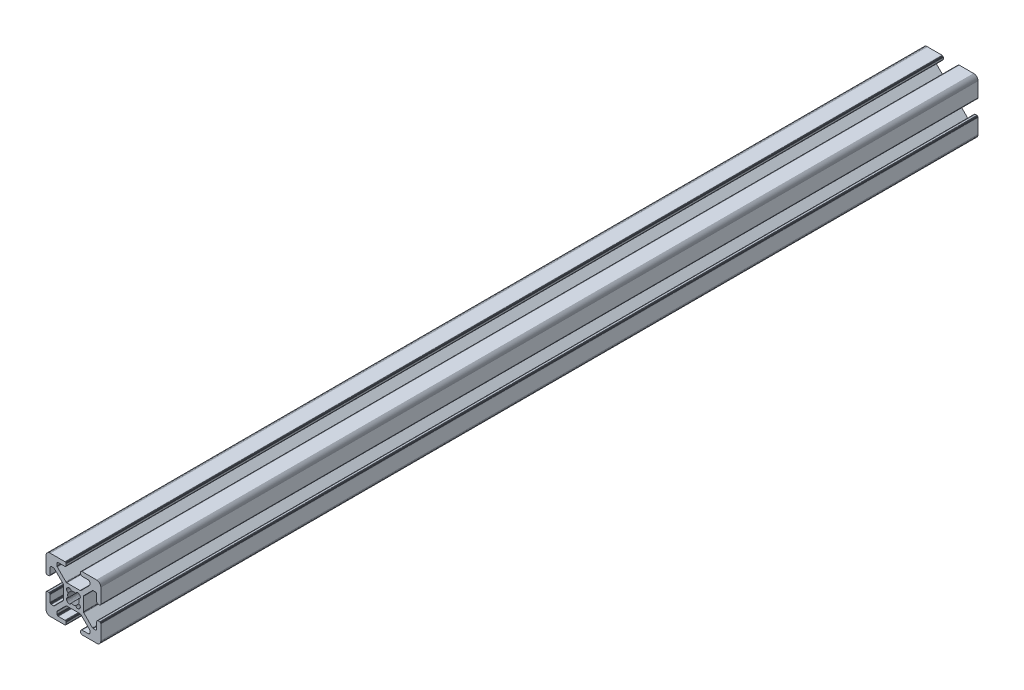
SolidWorks part; units mm, degrees
ref_plane "Front Plane" through (0, 0, 0) normal (0, 0, 1) x (1, 0, 0)
ref_plane "Top Plane" through (0, 0, 0) normal (0, 1, 0) x (1, 0, 0)
ref_plane "Right Plane" through (0, 0, 0) normal (1, 0, 0) x (0, 0, -1)
sketch "Model" plane through (0, 0, 0) normal (0, 0, 1) x (1, 0, 0)
  line L0 (949.3185, 626.4911) -> (949.2982, 626.4765)
  line L1 (949.2789, 626.4607) -> (949.2607, 626.4437)
  line L2 (946.8251, 623.8967) -> (946.8226, 623.8719)
  line L3 (949.2982, 626.4765) -> (949.2789, 626.4607)
  line L4 (946.9334, 624.1164) -> (949.2607, 626.4437)
  line L5 (949.3616, 626.516) -> (949.3396, 626.5042)
  line L6 (951.5709, 615.5372) -> (951.5806, 615.684)
  line L7 (946.2883, 614.588) -> (946.3355, 614.572)
  line L8 (946.8218, 620.2711) -> (946.8218, 623.847)
  line L9 (946.2436, 614.6101) -> (946.2883, 614.588)
  line L10 (948.4981, 615.8331) -> (948.5258, 615.8745)
  line L11 (946.1647, 614.6706) -> (946.2021, 614.6378)
  line L12 (946.842, 620.1486) -> (946.8508, 620.1253)
  line L13 (950.5066, 619.896) -> (950.4846, 619.8513)
  line L14 (946.2021, 614.6378) -> (946.2436, 614.6101)
  line L15 (950.5343, 619.9375) -> (950.5066, 619.896)
  line L16 (949.3396, 617.6138) -> (949.3616, 617.6021)
  line L17 (950.4685, 619.8041) -> (950.4588, 619.7553)
  line L18 (950.4588, 619.7553) -> (950.4556, 619.7055)
  line L19 (951.1996, 620.0865) -> (950.8366, 620.0865)
  line L20 (944.0806, 620.4874) -> (944.1836, 620.4908)
  line L21 (946.1379, 619.2062) -> (946.1197, 619.2232)
  line L22 (945.991, 619.2976) -> (945.9671, 619.3048)
  line L23 (950.2651, 617.6138) -> (950.3065, 617.6415)
  line L24 (950.2204, 617.5918) -> (950.2651, 617.6138)
  line L25 (945.0007, 623.9018) -> (944.9113, 623.8486)
  line L26 (951.3454, 620.0575) -> (951.2982, 620.0735)
  line L27 (950.5672, 624.1431) -> (950.6046, 624.1103)
  line L28 (950.5343, 624.1806) -> (950.5672, 624.1431)
  line L29 (946.0531, 614.94) -> (946.0563, 614.8903)
  line L30 (949.4804, 617.566) -> (949.5052, 617.5636)
  line L31 (945.0979, 623.9385) -> (945.0007, 623.9018)
  line L32 (946.1318, 628.5831) -> (946.1647, 628.5456)
  line L33 (946.1041, 628.6245) -> (946.1318, 628.5831)
  line L34 (950.344, 617.6744) -> (950.3768, 617.7118)
  line L35 (948.2455, 628.4308) -> (948.1958, 628.434)
  line L36 (948.2944, 628.421) -> (948.2455, 628.4308)
  line L37 (949.3185, 617.627) -> (949.3396, 617.6138)
  line L38 (950.6046, 620.0078) -> (950.5672, 619.9749)
  line L39 (951.5806, 628.434) -> (951.5709, 628.5809)
  line L40 (950.4266, 626.3201) -> (950.4045, 626.3648)
  line L41 (945.8701, 622.8898) -> (945.9233, 622.9791)
  line L42 (950.4426, 626.2729) -> (950.4266, 626.3201)
  line L43 (951.2511, 629.2295) -> (951.1404, 629.3265)
  line L44 (950.6046, 624.1103) -> (950.6461, 624.0826)
  line L45 (946.4341, 614.559) -> (950.4556, 614.559)
  line L46 (951.1404, 614.7915) -> (951.2511, 614.8885)
  line L47 (950.3065, 617.6415) -> (950.344, 617.6744)
  line L48 (950.6461, 624.0826) -> (950.6908, 624.0605)
  line L49 (948.4652, 628.3224) -> (948.4278, 628.3553)
  line L50 (945.8934, 619.317) -> (945.8685, 619.3178)
  line L51 (944.2863, 620.5009) -> (944.388, 620.5178)
  line L52 (951.5806, 619.7055) -> (951.5773, 619.7553)
  line L53 (950.738, 624.0445) -> (950.7868, 624.0348)
  line L54 (950.4588, 624.3628) -> (950.4685, 624.3139)
  line L55 (946.2021, 615.6053) -> (946.1647, 615.5724)
  line L56 (944.7673, 620.4183) -> (944.8328, 620.3375)
  line L57 (944.7171, 620.5093) -> (944.7673, 620.4183)
  line L58 (946.1647, 615.5724) -> (946.1318, 615.535)
  line L59 (950.8861, 629.4734) -> (950.7467, 629.5207)
  line L60 (944.6835, 620.6077) -> (944.7171, 620.5093)
  line L61 (950.4846, 624.2667) -> (950.5066, 624.222)
  line L62 (946.8226, 620.2462) -> (946.8251, 620.2214)
  line L63 (950.4685, 624.3139) -> (950.4846, 624.2667)
  line L64 (951.4315, 624.1103) -> (951.469, 624.1431)
  line L65 (946.1318, 615.535) -> (946.1041, 615.4935)
  line L66 (950.6024, 629.5494) -> (950.4556, 629.559)
  line L67 (951.5018, 624.1806) -> (951.5295, 624.222)
  line L68 (951.5806, 624.4125) -> (951.5806, 628.434)
  line L69 (950.5066, 624.222) -> (950.5343, 624.1806)
  line L70 (951.5295, 624.222) -> (951.5516, 624.2667)
  line L71 (944.0806, 619.3178) -> (945.8685, 619.3178)
  line L72 (951.5516, 624.2667) -> (951.5676, 624.3139)
  line L73 (951.469, 624.1431) -> (951.5018, 624.1806)
  line L74 (951.1404, 629.3265) -> (951.0181, 629.4083)
  line L75 (948.5258, 627.3181) -> (948.5375, 627.3401)
  line L76 (946.0821, 629.3238) -> (946.066, 629.2766)
  line L77 (951.5709, 628.5809) -> (951.5422, 628.7252)
  line L78 (945.9182, 619.3145) -> (945.8934, 619.317)
  line L79 (944.8328, 620.3375) -> (944.9113, 620.2695)
  line L80 (951.5422, 628.7252) -> (951.4949, 628.8645)
  line L81 (948.4652, 627.2392) -> (948.4823, 627.2574)
  line L82 (945.9428, 619.3105) -> (945.9182, 619.3145)
  line L83 (950.4556, 629.559) -> (946.4341, 629.559)
  line L84 (948.4981, 628.285) -> (948.4652, 628.3224)
  line L85 (946.1004, 624.879) -> (946.1197, 624.8948)
  line L86 (945.0007, 620.2163) -> (945.0979, 620.1796)
  line L87 (946.3843, 615.6808) -> (946.3355, 615.671)
  line L88 (948.1958, 615.684) -> (948.2455, 615.6873)
  line L89 (946.886, 620.0594) -> (946.9005, 620.0391)
  line L90 (946.9164, 624.0982) -> (946.9005, 624.0789)
  line L91 (949.3843, 626.5263) -> (949.3616, 626.516)
  line L92 (946.3355, 629.546) -> (946.2883, 629.53)
  line L93 (949.4558, 626.548) -> (949.4315, 626.5423)
  line L94 (950.6024, 614.5686) -> (950.7467, 614.5974)
  line L95 (946.4341, 629.559) -> (946.3843, 629.5558)
  line L96 (951.1996, 624.0315) -> (951.2493, 624.0348)
  line L97 (946.3843, 629.5558) -> (946.3355, 629.546)
  line L98 (946.1647, 628.5456) -> (946.2021, 628.5128)
  line L99 (950.0746, 617.5628) -> (949.5301, 617.5628)
  line L100 (950.0746, 617.5628) -> (950.1243, 617.566)
  line L101 (946.2021, 628.5128) -> (946.2436, 628.4851)
  line L102 (946.2883, 629.53) -> (946.2436, 629.508)
  line L103 (946.8611, 624.0155) -> (946.8508, 623.9928)
  line L104 (950.4523, 617.894) -> (950.4556, 617.9438)
  line L105 (946.8508, 623.9928) -> (946.842, 623.9694)
  line L106 (951.2493, 620.0833) -> (951.1996, 620.0865)
  line L107 (951.2982, 620.0735) -> (951.2493, 620.0833)
  line L108 (945.5945, 623.8542) -> (945.5044, 623.9059)
  line L109 (950.6461, 620.0355) -> (950.6046, 620.0078)
  line L110 (946.1318, 629.41) -> (946.1041, 629.3685)
  line L111 (945.6742, 623.7874) -> (945.5945, 623.8542)
  line L112 (946.1041, 629.3685) -> (946.0821, 629.3238)
  line L113 (951.5773, 619.7553) -> (951.5676, 619.8041)
  line L114 (948.5478, 628.1988) -> (948.5258, 628.2435)
  line L115 (948.5638, 628.1516) -> (948.5478, 628.1988)
  line L116 (950.4556, 626.1743) -> (950.4556, 624.4125)
  line L117 (945.9233, 622.9791) -> (945.96, 623.0764)
  line L118 (944.9113, 620.2695) -> (945.0007, 620.2163)
  line L119 (948.5566, 627.3861) -> (948.5638, 627.41)
  line L120 (946.3843, 614.5623) -> (946.4341, 614.559)
  line L121 (948.5736, 628.1028) -> (948.5638, 628.1516)
  line L122 (945.9233, 621.1389) -> (945.8701, 621.2282)
  line L123 (950.344, 626.4437) -> (950.3065, 626.4765)
  line L124 (945.991, 624.8205) -> (946.0143, 624.8293)
  line L125 (951.5676, 624.3139) -> (951.5773, 624.3628)
  line L126 (948.5478, 616.7553) -> (948.5375, 616.778)
  line L127 (948.5768, 616.6095) -> (948.5768, 616.065)
  line L128 (945.9671, 624.8133) -> (945.991, 624.8205)
  line L129 (946.3355, 614.572) -> (946.3843, 614.5623)
  line L130 (945.6387, 622.2647) -> (945.6218, 622.3665)
  line L131 (948.4652, 615.7956) -> (948.4981, 615.8331)
  line L132 (948.5566, 616.7319) -> (948.5478, 616.7553)
  line L133 (948.576, 627.4837) -> (948.5768, 627.5086)
  line L134 (945.9671, 619.3048) -> (945.9428, 619.3105)
  line L135 (946.059, 624.8513) -> (946.0802, 624.8645)
  line L136 (946.3355, 628.447) -> (946.3843, 628.4373)
  line L137 (951.3481, 629.1189) -> (951.2511, 629.2295)
  line L138 (948.5768, 628.053) -> (948.5768, 627.5086)
  line L139 (944.5871, 623.5468) -> (944.4884, 623.5768)
  line L140 (945.6303, 622.6955) -> (945.7213, 622.7458)
  line L141 (950.4045, 617.7533) -> (950.4266, 617.798)
  line L142 (945.9791, 623.1786) -> (945.9799, 623.2825)
  line L143 (945.9799, 623.2825) -> (945.9625, 623.385)
  line L144 (945.8021, 622.8112) -> (945.8701, 622.8898)
  line L145 (945.96, 623.0764) -> (945.9791, 623.1786)
  line L146 (945.7213, 622.7458) -> (945.8021, 622.8112)
  line L147 (950.1243, 617.566) -> (950.1732, 617.5758)
  line L148 (948.5638, 616.7081) -> (948.5566, 616.7319)
  line L149 (946.2436, 628.4851) -> (946.2883, 628.463)
  line L150 (948.5695, 627.4343) -> (948.5736, 627.4589)
  line L151 (946.1647, 629.4474) -> (946.1318, 629.41)
  line L152 (945.6742, 620.3306) -> (945.8089, 620.4653)
  line L153 (945.8757, 623.573) -> (945.8089, 623.6527)
  line L154 (946.2436, 629.508) -> (946.2021, 629.4803)
  line L155 (945.6218, 621.7516) -> (945.6387, 621.8533)
  line L156 (948.5126, 627.2969) -> (948.5258, 627.3181)
  line L157 (948.5638, 627.41) -> (948.5695, 627.4343)
  line L158 (948.5736, 627.4589) -> (948.576, 627.4837)
  line L159 (945.5044, 620.2122) -> (945.5945, 620.2639)
  line L160 (950.4426, 617.8452) -> (950.4523, 617.894)
  line L161 (946.1197, 624.8948) -> (946.1379, 624.9119)
  line L162 (945.5945, 620.2639) -> (945.6742, 620.3306)
  line L163 (950.3065, 626.4765) -> (950.2651, 626.5042)
  line L164 (946.4341, 615.684) -> (946.3843, 615.6808)
  line L165 (944.7673, 623.6998) -> (944.7171, 623.6088)
  line L166 (945.8757, 620.545) -> (945.9274, 620.6352)
  line L167 (948.5478, 615.9192) -> (948.5638, 615.9664)
  line L168 (945.9274, 620.6352) -> (945.9625, 620.7331)
  line L169 (950.1732, 626.5423) -> (950.1243, 626.552)
  line L170 (948.576, 616.6344) -> (948.5736, 616.6592)
  line L171 (950.1243, 626.552) -> (950.0746, 626.5553)
  line L172 (948.4981, 627.2766) -> (948.5126, 627.2969)
  line L173 (948.5258, 628.2435) -> (948.4981, 628.285)
  line L174 (948.5768, 628.053) -> (948.5736, 628.1028)
  line L175 (951.5516, 619.8513) -> (951.5295, 619.896)
  line L176 (951.5676, 619.8041) -> (951.5516, 619.8513)
  line L177 (946.0563, 615.3528) -> (946.0531, 615.303)
  line L178 (946.1041, 615.4935) -> (946.0821, 615.4488)
  line L179 (945.6387, 621.8533) -> (945.6488, 621.956)
  line L180 (946.037, 624.8396) -> (946.059, 624.8513)
  line L181 (950.4523, 626.224) -> (950.4426, 626.2729)
  line L182 (951.5773, 624.3628) -> (951.5806, 624.4125)
  line L183 (946.0531, 615.303) -> (946.0531, 614.94)
  line L184 (946.9005, 624.0789) -> (946.886, 624.0586)
  line L185 (946.0821, 615.4488) -> (946.066, 615.4016)
  line L186 (951.0181, 629.4083) -> (950.8861, 629.4734)
  line L187 (948.1958, 615.684) -> (946.4341, 615.684)
  line L188 (951.2982, 624.0445) -> (951.3454, 624.0605)
  line L189 (944.1836, 620.4908) -> (944.2863, 620.5009)
  line L190 (950.7467, 629.5207) -> (950.6024, 629.5494)
  line L191 (948.5375, 627.3401) -> (948.5478, 627.3628)
  line L192 (950.5672, 619.9749) -> (950.5343, 619.9375)
  line L193 (950.7868, 624.0348) -> (950.8366, 624.0315)
  line L194 (946.0531, 629.178) -> (946.0531, 628.815)
  line L195 (951.4949, 628.8645) -> (951.4298, 628.9965)
  line L196 (945.4065, 623.941) -> (945.3041, 623.9584)
  line L197 (945.8701, 621.2282) -> (945.8021, 621.3068)
  line L198 (950.3768, 626.4062) -> (950.344, 626.4437)
  line L199 (945.3041, 623.9584) -> (945.2001, 623.9575)
  line L200 (945.9625, 620.7331) -> (945.9799, 620.8355)
  line L201 (945.8089, 620.4653) -> (945.8757, 620.545)
  line L202 (948.2944, 615.697) -> (948.3416, 615.713)
  line L203 (948.2455, 615.6873) -> (948.2944, 615.697)
  line L204 (949.4804, 626.552) -> (949.4558, 626.548)
  line L205 (950.2204, 626.5263) -> (950.1732, 626.5423)
  line L206 (948.3416, 615.713) -> (948.3863, 615.7351)
  line L207 (945.7213, 621.3723) -> (945.6303, 621.4225)
  line L208 (950.4556, 626.1743) -> (950.4523, 626.224)
  line L209 (945.9799, 620.8355) -> (945.9791, 620.9395)
  line L210 (948.5768, 616.6095) -> (948.576, 616.6344)
  line L211 (948.5258, 615.8745) -> (948.5478, 615.9192)
  line L212 (945.9428, 624.8076) -> (945.9671, 624.8133)
  line L213 (945.2001, 623.9575) -> (945.0979, 623.9385)
  line L214 (945.96, 621.0417) -> (945.9233, 621.1389)
  line L215 (951.3454, 624.0605) -> (951.3901, 624.0826)
  line L216 (946.0802, 624.8645) -> (946.1004, 624.879)
  line L217 (951.5422, 615.3929) -> (951.5709, 615.5372)
  line L218 (945.6218, 622.3665) -> (945.5983, 622.4669)
  line L219 (951.3901, 624.0826) -> (951.4315, 624.1103)
  line L220 (949.5052, 626.5545) -> (949.4804, 626.552)
  line L221 (945.9791, 620.9395) -> (945.96, 621.0417)
  line L222 (946.0143, 619.2888) -> (945.991, 619.2976)
  line L223 (951.2493, 624.0348) -> (951.2982, 624.0445)
  line L224 (946.1197, 619.2232) -> (946.1004, 619.239)
  line L225 (951.4298, 628.9965) -> (951.3481, 629.1189)
  line L226 (951.2511, 614.8885) -> (951.3481, 614.9992)
  line L227 (946.1318, 614.7081) -> (946.1647, 614.6706)
  line L228 (944.6835, 623.5104) -> (944.5871, 623.5468)
  line L229 (948.5478, 627.3628) -> (948.5566, 627.3861)
  line L230 (950.4556, 624.4125) -> (950.4588, 624.3628)
  line L231 (946.0563, 629.2278) -> (946.0531, 629.178)
  line L232 (946.066, 629.2766) -> (946.0563, 629.2278)
  line L233 (944.388, 620.5178) -> (944.4884, 620.5412)
  line L234 (945.8685, 624.8003) -> (944.0806, 624.8003)
  line L235 (946.1004, 619.239) -> (946.0802, 619.2536)
  line L236 (951.4298, 615.1215) -> (951.4949, 615.2535)
  line L237 (946.3843, 628.4373) -> (946.4341, 628.434)
  line L238 (944.4884, 620.5412) -> (944.5871, 620.5713)
  line L239 (944.5871, 620.5713) -> (944.6835, 620.6077)
  line L240 (946.8291, 620.1968) -> (946.8348, 620.1725)
  line L241 (946.8508, 620.1253) -> (946.8611, 620.1026)
  line L242 (946.8218, 620.2711) -> (946.8226, 620.2462)
  line L243 (946.8226, 623.8719) -> (946.8218, 623.847)
  line L244 (946.8291, 623.9213) -> (946.8251, 623.8967)
  line L245 (949.4315, 626.5423) -> (949.4077, 626.5351)
  line L246 (949.4077, 626.5351) -> (949.3843, 626.5263)
  line L247 (949.3396, 626.5042) -> (949.3185, 626.4911)
  line L248 (946.9334, 624.1164) -> (946.9164, 624.0982)
  line L249 (944.1836, 623.6273) -> (944.0806, 623.6307)
  line L250 (951.5295, 619.896) -> (951.5018, 619.9375)
  line L251 (944.388, 623.6003) -> (944.2863, 623.6171)
  line L252 (950.4266, 617.798) -> (950.4426, 617.8452)
  line L253 (946.842, 623.9694) -> (946.8348, 623.9456)
  line L254 (950.4556, 619.7055) -> (950.4556, 617.9438)
  line L255 (949.2789, 617.6573) -> (949.2982, 617.6415)
  line L256 (946.8611, 620.1026) -> (946.8729, 620.0806)
  line L257 (946.8348, 620.1725) -> (946.842, 620.1486)
  line L258 (949.2607, 617.6744) -> (946.9334, 620.0017)
  line L259 (945.6522, 622.059) -> (945.6488, 622.1621)
  line L260 (945.6488, 621.956) -> (945.6522, 622.059)
  line L261 (946.1041, 614.7495) -> (946.1318, 614.7081)
  line L262 (944.8328, 623.7805) -> (944.7673, 623.6998)
  line L263 (946.0821, 614.7942) -> (946.1041, 614.7495)
  line L264 (946.9164, 620.0199) -> (946.9334, 620.0017)
  line L265 (944.7171, 623.6088) -> (944.6835, 623.5104)
  line L266 (946.8729, 620.0806) -> (946.886, 620.0594)
  line L267 (945.5683, 622.5655) -> (945.5319, 622.662)
  line L268 (945.3041, 620.1597) -> (945.4065, 620.1771)
  line L269 (950.4556, 614.559) -> (950.6024, 614.5686)
  line L270 (945.6303, 621.4225) -> (945.5319, 621.456)
  line L271 (946.8251, 620.2214) -> (946.8291, 620.1968)
  line L272 (945.5983, 621.6512) -> (945.6218, 621.7516)
  line L273 (945.6488, 622.1621) -> (945.6387, 622.2647)
  line L274 (945.2001, 620.1605) -> (945.3041, 620.1597)
  line L275 (946.066, 614.8414) -> (946.0821, 614.7942)
  line L276 (951.5806, 615.684) -> (951.5806, 619.7055)
  line L277 (945.8685, 624.8003) -> (945.8934, 624.8011)
  line L278 (945.8934, 624.8011) -> (945.9182, 624.8035)
  line L279 (946.886, 624.0586) -> (946.8729, 624.0375)
  line L280 (946.8729, 624.0375) -> (946.8611, 624.0155)
  line L281 (948.5638, 615.9664) -> (948.5736, 616.0153)
  line L282 (948.4823, 627.2574) -> (948.4981, 627.2766)
  line L283 (950.8366, 624.0315) -> (951.1996, 624.0315)
  line L284 (945.5044, 623.9059) -> (945.4065, 623.941)
  line L285 (950.4846, 619.8513) -> (950.4685, 619.8041)
  line L286 (948.5736, 616.0153) -> (948.5768, 616.065)
  line L287 (945.8021, 621.3068) -> (945.7213, 621.3723)
  line L288 (950.8366, 620.0865) -> (950.7868, 620.0833)
  line L289 (946.8348, 623.9456) -> (946.8291, 623.9213)
  line L290 (949.5301, 626.5553) -> (950.0746, 626.5553)
  line L291 (945.5683, 621.5525) -> (945.5983, 621.6512)
  line L292 (949.2982, 617.6415) -> (949.3185, 617.627)
  line L293 (950.1732, 617.5758) -> (950.2204, 617.5918)
  line L294 (951.3901, 620.0355) -> (951.3454, 620.0575)
  line L295 (948.5375, 616.778) -> (948.5258, 616.8)
  line L296 (951.3481, 614.9992) -> (951.4298, 615.1215)
  line L297 (951.4315, 620.0078) -> (951.3901, 620.0355)
  line L298 (948.4981, 616.8414) -> (948.4823, 616.8607)
  line L299 (948.3416, 628.405) -> (948.2944, 628.421)
  line L300 (950.2651, 626.5042) -> (950.2204, 626.5263)
  line L301 (949.2607, 617.6744) -> (949.2789, 617.6573)
  line L302 (948.5126, 616.8211) -> (948.4981, 616.8414)
  line L303 (946.0531, 628.815) -> (946.0563, 628.7653)
  line L304 (951.469, 619.9749) -> (951.4315, 620.0078)
  line L305 (948.4652, 627.2392) -> (946.1379, 624.9119)
  line L306 (946.066, 615.4016) -> (946.0563, 615.3528)
  line L307 (950.7868, 620.0833) -> (950.738, 620.0735)
  line L308 (948.4823, 616.8607) -> (948.4652, 616.8789)
  line L309 (946.0563, 628.7653) -> (946.066, 628.7164)
  line L310 (951.5018, 619.9375) -> (951.469, 619.9749)
  line L311 (946.1379, 619.2062) -> (948.4652, 616.8789)
  line L312 (946.2883, 628.463) -> (946.3355, 628.447)
  line L313 (946.4341, 628.434) -> (948.1958, 628.434)
  line L314 (944.2863, 623.6171) -> (944.1836, 623.6273)
  line L315 (948.3863, 628.383) -> (948.3416, 628.405)
  line L316 (950.6908, 620.0575) -> (950.6461, 620.0355)
  line L317 (946.0143, 624.8293) -> (946.037, 624.8396)
  line L318 (950.738, 620.0735) -> (950.6908, 620.0575)
  line L319 (946.9005, 620.0391) -> (946.9164, 620.0199)
  line L320 (944.4884, 623.5768) -> (944.388, 623.6003)
  line L321 (950.3768, 617.7118) -> (950.4045, 617.7533)
  line L322 (948.4278, 628.3553) -> (948.3863, 628.383)
  line L323 (949.4558, 617.5701) -> (949.4804, 617.566)
  line L324 (949.5052, 617.5636) -> (949.5301, 617.5628)
  line L325 (946.066, 628.7164) -> (946.0821, 628.6692)
  line L326 (946.0821, 628.6692) -> (946.1041, 628.6245)
  line L327 (950.8861, 614.6447) -> (951.0181, 614.7097)
  line L328 (945.0979, 620.1796) -> (945.2001, 620.1605)
  line L329 (948.4278, 615.7628) -> (948.4652, 615.7956)
  line L330 (948.3863, 615.7351) -> (948.4278, 615.7628)
  line L331 (948.5736, 616.6592) -> (948.5695, 616.6838)
  line L332 (950.7467, 614.5974) -> (950.8861, 614.6447)
  line L333 (948.5695, 616.6838) -> (948.5638, 616.7081)
  line L334 (945.8089, 623.6527) -> (945.6742, 623.7874)
  line L335 (945.5319, 621.456) -> (945.5683, 621.5525)
  line L336 (945.9274, 623.4828) -> (945.8757, 623.573)
  line L337 (945.5983, 622.4669) -> (945.5683, 622.5655)
  line L338 (949.4077, 617.583) -> (949.4315, 617.5758)
  line L339 (949.4315, 617.5758) -> (949.4558, 617.5701)
  line L340 (945.9625, 623.385) -> (945.9274, 623.4828)
  line L341 (946.037, 619.2785) -> (946.0143, 619.2888)
  line L342 (946.0802, 619.2536) -> (946.059, 619.2667)
  line L343 (946.2436, 615.633) -> (946.2021, 615.6053)
  line L344 (944.9113, 623.8486) -> (944.8328, 623.7805)
  line L345 (950.6908, 624.0605) -> (950.738, 624.0445)
  line L346 (950.4045, 626.3648) -> (950.3768, 626.4062)
  line L347 (946.2021, 629.4803) -> (946.1647, 629.4474)
  line L348 (946.059, 619.2667) -> (946.037, 619.2785)
  line L349 (949.3843, 617.5918) -> (949.4077, 617.583)
  line L350 (946.0563, 614.8903) -> (946.066, 614.8414)
  line L351 (949.3616, 617.6021) -> (949.3843, 617.5918)
  line L352 (948.5258, 616.8) -> (948.5126, 616.8211)
  line L353 (945.4065, 620.1771) -> (945.5044, 620.2122)
  line L354 (949.5301, 626.5553) -> (949.5052, 626.5545)
  line L355 (951.4949, 615.2535) -> (951.5422, 615.3929)
  line L356 (945.5319, 622.662) -> (945.6303, 622.6955)
  line L357 (946.3355, 615.671) -> (946.2883, 615.655)
  line L358 (946.2883, 615.655) -> (946.2436, 615.633)
  line L359 (945.9182, 624.8035) -> (945.9428, 624.8076)
  line L360 (951.0181, 614.7097) -> (951.1404, 614.7915)
  line L361 (938.8427, 626.4911) -> (938.8629, 626.4765)
  line L362 (938.8822, 626.4607) -> (938.9004, 626.4437)
  line L363 (941.3361, 623.8967) -> (941.3385, 623.8719)
  line L364 (938.8629, 626.4765) -> (938.8822, 626.4607)
  line L365 (941.2277, 624.1164) -> (938.9004, 626.4437)
  line L366 (938.7995, 626.516) -> (938.8215, 626.5042)
  line L367 (936.5902, 615.5372) -> (936.5806, 615.684)
  line L368 (941.8729, 614.588) -> (941.8257, 614.572)
  line L369 (941.3393, 620.2711) -> (941.3393, 623.847)
  line L370 (941.9176, 614.6101) -> (941.8729, 614.588)
  line L371 (939.663, 615.8331) -> (939.6354, 615.8745)
  line L372 (941.9965, 614.6706) -> (941.959, 614.6378)
  line L373 (941.3191, 620.1486) -> (941.3103, 620.1253)
  line L374 (937.6545, 619.896) -> (937.6766, 619.8513)
  line L375 (941.959, 614.6378) -> (941.9176, 614.6101)
  line L376 (937.6268, 619.9375) -> (937.6545, 619.896)
  line L377 (938.8215, 617.6138) -> (938.7995, 617.6021)
  line L378 (937.6926, 619.8041) -> (937.7023, 619.7553)
  line L379 (937.7023, 619.7553) -> (937.7056, 619.7055)
  line L380 (936.9616, 620.0865) -> (937.3246, 620.0865)
  line L381 (944.0806, 620.4874) -> (943.9775, 620.4908)
  line L382 (942.0232, 619.2062) -> (942.0414, 619.2232)
  line L383 (942.1702, 619.2976) -> (942.194, 619.3048)
  line L384 (937.8961, 617.6138) -> (937.8546, 617.6415)
  line L385 (937.9408, 617.5918) -> (937.8961, 617.6138)
  line L386 (943.1605, 623.9018) -> (943.2498, 623.8486)
  line L387 (936.8158, 620.0575) -> (936.863, 620.0735)
  line L388 (937.594, 624.1431) -> (937.5565, 624.1103)
  line L389 (937.6268, 624.1806) -> (937.594, 624.1431)
  line L390 (942.1081, 614.94) -> (942.1048, 614.8903)
  line L391 (938.6807, 617.566) -> (938.6559, 617.5636)
  line L392 (943.0632, 623.9385) -> (943.1605, 623.9018)
  line L393 (942.0293, 628.5831) -> (941.9965, 628.5456)
  line L394 (942.057, 628.6245) -> (942.0293, 628.5831)
  line L395 (937.8172, 617.6744) -> (937.7843, 617.7118)
  line L396 (939.9156, 628.4308) -> (939.9653, 628.434)
  line L397 (939.8667, 628.421) -> (939.9156, 628.4308)
  line L398 (938.8427, 617.627) -> (938.8215, 617.6138)
  line L399 (937.5565, 620.0078) -> (937.594, 619.9749)
  line L400 (936.5806, 628.434) -> (936.5902, 628.5809)
  line L401 (937.7346, 626.3201) -> (937.7566, 626.3648)
  line L402 (942.291, 622.8898) -> (942.2378, 622.9791)
  line L403 (937.7185, 626.2729) -> (937.7346, 626.3201)
  line L404 (936.9101, 629.2295) -> (937.0207, 629.3265)
  line L405 (937.5565, 624.1103) -> (937.5151, 624.0826)
  line L406 (941.7271, 614.559) -> (937.7056, 614.559)
  line L407 (937.0207, 614.7915) -> (936.9101, 614.8885)
  line L408 (937.8546, 617.6415) -> (937.8172, 617.6744)
  line L409 (937.5151, 624.0826) -> (937.4704, 624.0605)
  line L410 (939.6959, 628.3224) -> (939.7334, 628.3553)
  line L411 (942.2677, 619.317) -> (942.2926, 619.3178)
  line L412 (943.8749, 620.5009) -> (943.7731, 620.5178)
  line L413 (936.5806, 619.7055) -> (936.5838, 619.7553)
  line L414 (937.4232, 624.0445) -> (937.3743, 624.0348)
  line L415 (937.7023, 624.3628) -> (937.6926, 624.3139)
  line L416 (941.959, 615.6053) -> (941.9965, 615.5724)
  line L417 (943.3938, 620.4183) -> (943.3284, 620.3375)
  line L418 (943.4441, 620.5093) -> (943.3938, 620.4183)
  line L419 (941.9965, 615.5724) -> (942.0293, 615.535)
  line L420 (937.275, 629.4734) -> (937.4144, 629.5207)
  line L421 (943.4776, 620.6077) -> (943.4441, 620.5093)
  line L422 (937.6766, 624.2667) -> (937.6545, 624.222)
  line L423 (941.3385, 620.2462) -> (941.3361, 620.2214)
  line L424 (937.6926, 624.3139) -> (937.6766, 624.2667)
  line L425 (936.7296, 624.1103) -> (936.6922, 624.1431)
  line L426 (942.0293, 615.535) -> (942.057, 615.4935)
  line L427 (937.5587, 629.5494) -> (937.7056, 629.559)
  line L428 (936.6593, 624.1806) -> (936.6316, 624.222)
  line L429 (936.5806, 624.4125) -> (936.5806, 628.434)
  line L430 (937.6545, 624.222) -> (937.6268, 624.1806)
  line L431 (936.6316, 624.222) -> (936.6096, 624.2667)
  line L432 (944.0806, 619.3178) -> (942.2926, 619.3178)
  line L433 (936.6096, 624.2667) -> (936.5935, 624.3139)
  line L434 (936.6922, 624.1431) -> (936.6593, 624.1806)
  line L435 (937.0207, 629.3265) -> (937.1431, 629.4083)
  line L436 (939.6354, 627.3181) -> (939.6236, 627.3401)
  line L437 (942.0791, 629.3238) -> (942.0951, 629.2766)
  line L438 (936.5902, 628.5809) -> (936.6189, 628.7252)
  line L439 (942.2429, 619.3145) -> (942.2677, 619.317)
  line L440 (943.3284, 620.3375) -> (943.2498, 620.2695)
  line L441 (936.6189, 628.7252) -> (936.6662, 628.8645)
  line L442 (939.6959, 627.2392) -> (939.6789, 627.2574)
  line L443 (942.2183, 619.3105) -> (942.2429, 619.3145)
  line L444 (937.7056, 629.559) -> (941.7271, 629.559)
  line L445 (939.663, 628.285) -> (939.6959, 628.3224)
  line L446 (942.0607, 624.879) -> (942.0414, 624.8948)
  line L447 (943.1605, 620.2163) -> (943.0632, 620.1796)
  line L448 (941.7768, 615.6808) -> (941.8257, 615.671)
  line L449 (939.9653, 615.684) -> (939.9156, 615.6873)
  line L450 (941.2751, 620.0594) -> (941.2606, 620.0391)
  line L451 (941.2448, 624.0982) -> (941.2606, 624.0789)
  line L452 (938.7768, 626.5263) -> (938.7995, 626.516)
  line L453 (941.8257, 629.546) -> (941.8729, 629.53)
  line L454 (938.7053, 626.548) -> (938.7296, 626.5423)
  line L455 (937.5587, 614.5686) -> (937.4144, 614.5974)
  line L456 (941.7271, 629.559) -> (941.7768, 629.5558)
  line L457 (936.9616, 624.0315) -> (936.9118, 624.0348)
  line L458 (941.7768, 629.5558) -> (941.8257, 629.546)
  line L459 (941.9965, 628.5456) -> (941.959, 628.5128)
  line L460 (938.0866, 617.5628) -> (938.631, 617.5628)
  line L461 (938.0866, 617.5628) -> (938.0368, 617.566)
  line L462 (941.959, 628.5128) -> (941.9176, 628.4851)
  line L463 (941.8729, 629.53) -> (941.9176, 629.508)
  line L464 (941.3, 624.0155) -> (941.3103, 623.9928)
  line L465 (937.7088, 617.894) -> (937.7056, 617.9438)
  line L466 (941.3103, 623.9928) -> (941.3191, 623.9694)
  line L467 (936.9118, 620.0833) -> (936.9616, 620.0865)
  line L468 (936.863, 620.0735) -> (936.9118, 620.0833)
  line L469 (942.5666, 623.8542) -> (942.6567, 623.9059)
  line L470 (937.5151, 620.0355) -> (937.5565, 620.0078)
  line L471 (942.0293, 629.41) -> (942.057, 629.3685)
  line L472 (942.4869, 623.7874) -> (942.5666, 623.8542)
  line L473 (942.057, 629.3685) -> (942.0791, 629.3238)
  line L474 (936.5838, 619.7553) -> (936.5935, 619.8041)
  line L475 (939.6133, 628.1988) -> (939.6354, 628.2435)
  line L476 (939.5973, 628.1516) -> (939.6133, 628.1988)
  line L477 (937.7056, 626.1743) -> (937.7056, 624.4125)
  line L478 (942.2378, 622.9791) -> (942.2011, 623.0764)
  line L479 (943.2498, 620.2695) -> (943.1605, 620.2163)
  line L480 (939.6045, 627.3861) -> (939.5973, 627.41)
  line L481 (941.7768, 614.5623) -> (941.7271, 614.559)
  line L482 (939.5876, 628.1028) -> (939.5973, 628.1516)
  line L483 (942.2378, 621.1389) -> (942.291, 621.2282)
  line L484 (937.8172, 626.4437) -> (937.8546, 626.4765)
  line L485 (942.1702, 624.8205) -> (942.1468, 624.8293)
  line L486 (936.5935, 624.3139) -> (936.5838, 624.3628)
  line L487 (939.6133, 616.7553) -> (939.6236, 616.778)
  line L488 (939.5843, 616.6095) -> (939.5843, 616.065)
  line L489 (942.194, 624.8133) -> (942.1702, 624.8205)
  line L490 (941.8257, 614.572) -> (941.7768, 614.5623)
  line L491 (942.5225, 622.2647) -> (942.5393, 622.3665)
  line L492 (939.6959, 615.7956) -> (939.663, 615.8331)
  line L493 (939.6045, 616.7319) -> (939.6133, 616.7553)
  line L494 (939.5851, 627.4837) -> (939.5843, 627.5086)
  line L495 (942.194, 619.3048) -> (942.2183, 619.3105)
  line L496 (942.1021, 624.8513) -> (942.081, 624.8645)
  line L497 (941.8257, 628.447) -> (941.7768, 628.4373)
  line L498 (936.813, 629.1189) -> (936.9101, 629.2295)
  line L499 (939.5843, 628.053) -> (939.5843, 627.5086)
  line L500 (943.5741, 623.5468) -> (943.6727, 623.5768)
  line L501 (942.5308, 622.6955) -> (942.4398, 622.7458)
  line L502 (937.7566, 617.7533) -> (937.7346, 617.798)
  line L503 (942.182, 623.1786) -> (942.1812, 623.2825)
  line L504 (942.1812, 623.2825) -> (942.1986, 623.385)
  line L505 (942.359, 622.8112) -> (942.291, 622.8898)
  line L506 (942.2011, 623.0764) -> (942.182, 623.1786)
  line L507 (942.4398, 622.7458) -> (942.359, 622.8112)
  line L508 (938.0368, 617.566) -> (937.988, 617.5758)
  line L509 (939.5973, 616.7081) -> (939.6045, 616.7319)
  line L510 (941.9176, 628.4851) -> (941.8729, 628.463)
  line L511 (939.5916, 627.4343) -> (939.5876, 627.4589)
  line L512 (941.9965, 629.4474) -> (942.0293, 629.41)
  line L513 (942.4869, 620.3306) -> (942.3522, 620.4653)
  line L514 (942.2854, 623.573) -> (942.3522, 623.6527)
  line L515 (941.9176, 629.508) -> (941.959, 629.4803)
  line L516 (942.5393, 621.7516) -> (942.5225, 621.8533)
  line L517 (939.6485, 627.2969) -> (939.6354, 627.3181)
  line L518 (939.5973, 627.41) -> (939.5916, 627.4343)
  line L519 (939.5876, 627.4589) -> (939.5851, 627.4837)
  line L520 (942.6567, 620.2122) -> (942.5666, 620.2639)
  line L521 (937.7185, 617.8452) -> (937.7088, 617.894)
  line L522 (942.0414, 624.8948) -> (942.0232, 624.9119)
  line L523 (942.5666, 620.2639) -> (942.4869, 620.3306)
  line L524 (937.8546, 626.4765) -> (937.8961, 626.5042)
  line L525 (941.7271, 615.684) -> (941.7768, 615.6808)
  line L526 (943.3938, 623.6998) -> (943.4441, 623.6088)
  line L527 (942.2854, 620.545) -> (942.2337, 620.6352)
  line L528 (939.6133, 615.9192) -> (939.5973, 615.9664)
  line L529 (942.2337, 620.6352) -> (942.1986, 620.7331)
  line L530 (937.988, 626.5423) -> (938.0368, 626.552)
  line L531 (939.5851, 616.6344) -> (939.5876, 616.6592)
  line L532 (938.0368, 626.552) -> (938.0866, 626.5553)
  line L533 (939.663, 627.2766) -> (939.6485, 627.2969)
  line L534 (939.6354, 628.2435) -> (939.663, 628.285)
  line L535 (939.5843, 628.053) -> (939.5876, 628.1028)
  line L536 (936.6096, 619.8513) -> (936.6316, 619.896)
  line L537 (936.5935, 619.8041) -> (936.6096, 619.8513)
  line L538 (942.1048, 615.3528) -> (942.1081, 615.303)
  line L539 (942.057, 615.4935) -> (942.0791, 615.4488)
  line L540 (942.5225, 621.8533) -> (942.5123, 621.956)
  line L541 (942.1241, 624.8396) -> (942.1021, 624.8513)
  line L542 (937.7088, 626.224) -> (937.7185, 626.2729)
  line L543 (936.5838, 624.3628) -> (936.5806, 624.4125)
  line L544 (942.1081, 615.303) -> (942.1081, 614.94)
  line L545 (941.2606, 624.0789) -> (941.2751, 624.0586)
  line L546 (942.0791, 615.4488) -> (942.0951, 615.4016)
  line L547 (937.1431, 629.4083) -> (937.275, 629.4734)
  line L548 (939.9653, 615.684) -> (941.7271, 615.684)
  line L549 (936.863, 624.0445) -> (936.8158, 624.0605)
  line L550 (943.9775, 620.4908) -> (943.8749, 620.5009)
  line L551 (937.4144, 629.5207) -> (937.5587, 629.5494)
  line L552 (939.6236, 627.3401) -> (939.6133, 627.3628)
  line L553 (937.594, 619.9749) -> (937.6268, 619.9375)
  line L554 (937.3743, 624.0348) -> (937.3246, 624.0315)
  line L555 (942.1081, 629.178) -> (942.1081, 628.815)
  line L556 (936.6662, 628.8645) -> (936.7313, 628.9965)
  line L557 (942.7546, 623.941) -> (942.8571, 623.9584)
  line L558 (942.291, 621.2282) -> (942.359, 621.3068)
  line L559 (937.7843, 626.4062) -> (937.8172, 626.4437)
  line L560 (942.8571, 623.9584) -> (942.961, 623.9575)
  line L561 (942.1986, 620.7331) -> (942.1812, 620.8355)
  line L562 (942.3522, 620.4653) -> (942.2854, 620.545)
  line L563 (939.8667, 615.697) -> (939.8195, 615.713)
  line L564 (939.9156, 615.6873) -> (939.8667, 615.697)
  line L565 (938.6807, 626.552) -> (938.7053, 626.548)
  line L566 (937.9408, 626.5263) -> (937.988, 626.5423)
  line L567 (939.8195, 615.713) -> (939.7748, 615.7351)
  line L568 (942.4398, 621.3723) -> (942.5308, 621.4225)
  line L569 (937.7056, 626.1743) -> (937.7088, 626.224)
  line L570 (942.1812, 620.8355) -> (942.182, 620.9395)
  line L571 (939.5843, 616.6095) -> (939.5851, 616.6344)
  line L572 (939.6354, 615.8745) -> (939.6133, 615.9192)
  line L573 (942.2183, 624.8076) -> (942.194, 624.8133)
  line L574 (942.961, 623.9575) -> (943.0632, 623.9385)
  line L575 (942.2011, 621.0417) -> (942.2378, 621.1389)
  line L576 (936.8158, 624.0605) -> (936.7711, 624.0826)
  line L577 (942.081, 624.8645) -> (942.0607, 624.879)
  line L578 (936.6189, 615.3929) -> (936.5902, 615.5372)
  line L579 (942.5393, 622.3665) -> (942.5628, 622.4669)
  line L580 (936.7711, 624.0826) -> (936.7296, 624.1103)
  line L581 (938.6559, 626.5545) -> (938.6807, 626.552)
  line L582 (942.182, 620.9395) -> (942.2011, 621.0417)
  line L583 (942.1468, 619.2888) -> (942.1702, 619.2976)
  line L584 (936.9118, 624.0348) -> (936.863, 624.0445)
  line L585 (942.0414, 619.2232) -> (942.0607, 619.239)
  line L586 (936.7313, 628.9965) -> (936.813, 629.1189)
  line L587 (936.9101, 614.8885) -> (936.813, 614.9992)
  line L588 (942.0293, 614.7081) -> (941.9965, 614.6706)
  line L589 (943.4776, 623.5104) -> (943.5741, 623.5468)
  line L590 (939.6133, 627.3628) -> (939.6045, 627.3861)
  line L591 (937.7056, 624.4125) -> (937.7023, 624.3628)
  line L592 (942.1048, 629.2278) -> (942.1081, 629.178)
  line L593 (942.0951, 629.2766) -> (942.1048, 629.2278)
  line L594 (943.7731, 620.5178) -> (943.6727, 620.5412)
  line L595 (942.2926, 624.8003) -> (944.0806, 624.8003)
  line L596 (942.0607, 619.239) -> (942.081, 619.2536)
  line L597 (936.7313, 615.1215) -> (936.6662, 615.2535)
  line L598 (941.7768, 628.4373) -> (941.7271, 628.434)
  line L599 (943.6727, 620.5412) -> (943.5741, 620.5713)
  line L600 (943.5741, 620.5713) -> (943.4776, 620.6077)
  line L601 (941.332, 620.1968) -> (941.3263, 620.1725)
  line L602 (941.3103, 620.1253) -> (941.3, 620.1026)
  line L603 (941.3393, 620.2711) -> (941.3385, 620.2462)
  line L604 (941.3385, 623.8719) -> (941.3393, 623.847)
  line L605 (941.332, 623.9213) -> (941.3361, 623.8967)
  line L606 (938.7296, 626.5423) -> (938.7535, 626.5351)
  line L607 (938.7535, 626.5351) -> (938.7768, 626.5263)
  line L608 (938.8215, 626.5042) -> (938.8427, 626.4911)
  line L609 (941.2277, 624.1164) -> (941.2448, 624.0982)
  line L610 (943.9775, 623.6273) -> (944.0806, 623.6307)
  line L611 (936.6316, 619.896) -> (936.6593, 619.9375)
  line L612 (943.7731, 623.6003) -> (943.8749, 623.6171)
  line L613 (937.7346, 617.798) -> (937.7185, 617.8452)
  line L614 (941.3191, 623.9694) -> (941.3263, 623.9456)
  line L615 (937.7056, 619.7055) -> (937.7056, 617.9438)
  line L616 (938.8822, 617.6573) -> (938.8629, 617.6415)
  line L617 (941.3, 620.1026) -> (941.2883, 620.0806)
  line L618 (941.3263, 620.1725) -> (941.3191, 620.1486)
  line L619 (938.9004, 617.6744) -> (941.2277, 620.0017)
  line L620 (942.5089, 622.059) -> (942.5123, 622.1621)
  line L621 (942.5123, 621.956) -> (942.5089, 622.059)
  line L622 (942.057, 614.7495) -> (942.0293, 614.7081)
  line L623 (943.3284, 623.7805) -> (943.3938, 623.6998)
  line L624 (942.0791, 614.7942) -> (942.057, 614.7495)
  line L625 (941.2448, 620.0199) -> (941.2277, 620.0017)
  line L626 (943.4441, 623.6088) -> (943.4776, 623.5104)
  line L627 (941.2883, 620.0806) -> (941.2751, 620.0594)
  line L628 (942.5928, 622.5655) -> (942.6292, 622.662)
  line L629 (942.8571, 620.1597) -> (942.7546, 620.1771)
  line L630 (937.7056, 614.559) -> (937.5587, 614.5686)
  line L631 (942.5308, 621.4225) -> (942.6292, 621.456)
  line L632 (941.3361, 620.2214) -> (941.332, 620.1968)
  line L633 (942.5628, 621.6512) -> (942.5393, 621.7516)
  line L634 (942.5123, 622.1621) -> (942.5225, 622.2647)
  line L635 (942.961, 620.1605) -> (942.8571, 620.1597)
  line L636 (942.0951, 614.8414) -> (942.0791, 614.7942)
  line L637 (936.5806, 615.684) -> (936.5806, 619.7055)
  line L638 (942.2926, 624.8003) -> (942.2677, 624.8011)
  line L639 (942.2677, 624.8011) -> (942.2429, 624.8035)
  line L640 (941.2751, 624.0586) -> (941.2883, 624.0375)
  line L641 (941.2883, 624.0375) -> (941.3, 624.0155)
  line L642 (939.5973, 615.9664) -> (939.5876, 616.0153)
  line L643 (939.6789, 627.2574) -> (939.663, 627.2766)
  line L644 (937.3246, 624.0315) -> (936.9616, 624.0315)
  line L645 (942.6567, 623.9059) -> (942.7546, 623.941)
  line L646 (937.6766, 619.8513) -> (937.6926, 619.8041)
  line L647 (939.5876, 616.0153) -> (939.5843, 616.065)
  line L648 (942.359, 621.3068) -> (942.4398, 621.3723)
  line L649 (937.3246, 620.0865) -> (937.3743, 620.0833)
  line L650 (941.3263, 623.9456) -> (941.332, 623.9213)
  line L651 (938.631, 626.5553) -> (938.0866, 626.5553)
  line L652 (942.5928, 621.5525) -> (942.5628, 621.6512)
  line L653 (938.8629, 617.6415) -> (938.8427, 617.627)
  line L654 (937.988, 617.5758) -> (937.9408, 617.5918)
  line L655 (936.7711, 620.0355) -> (936.8158, 620.0575)
  line L656 (939.6236, 616.778) -> (939.6354, 616.8)
  line L657 (936.813, 614.9992) -> (936.7313, 615.1215)
  line L658 (936.7296, 620.0078) -> (936.7711, 620.0355)
  line L659 (939.663, 616.8414) -> (939.6789, 616.8607)
  line L660 (939.8195, 628.405) -> (939.8667, 628.421)
  line L661 (937.8961, 626.5042) -> (937.9408, 626.5263)
  line L662 (938.9004, 617.6744) -> (938.8822, 617.6573)
  line L663 (939.6485, 616.8211) -> (939.663, 616.8414)
  line L664 (942.1081, 628.815) -> (942.1048, 628.7653)
  line L665 (936.6922, 619.9749) -> (936.7296, 620.0078)
  line L666 (939.6959, 627.2392) -> (942.0232, 624.9119)
  line L667 (942.0951, 615.4016) -> (942.1048, 615.3528)
  line L668 (937.3743, 620.0833) -> (937.4232, 620.0735)
  line L669 (939.6789, 616.8607) -> (939.6959, 616.8789)
  line L670 (942.1048, 628.7653) -> (942.0951, 628.7164)
  line L671 (936.6593, 619.9375) -> (936.6922, 619.9749)
  line L672 (942.0232, 619.2062) -> (939.6959, 616.8789)
  line L673 (941.8729, 628.463) -> (941.8257, 628.447)
  line L674 (941.7271, 628.434) -> (939.9653, 628.434)
  line L675 (943.8749, 623.6171) -> (943.9775, 623.6273)
  line L676 (939.7748, 628.383) -> (939.8195, 628.405)
  line L677 (937.4704, 620.0575) -> (937.5151, 620.0355)
  line L678 (942.1468, 624.8293) -> (942.1241, 624.8396)
  line L679 (937.4232, 620.0735) -> (937.4704, 620.0575)
  line L680 (941.2606, 620.0391) -> (941.2448, 620.0199)
  line L681 (943.6727, 623.5768) -> (943.7731, 623.6003)
  line L682 (937.7843, 617.7118) -> (937.7566, 617.7533)
  line L683 (939.7334, 628.3553) -> (939.7748, 628.383)
  line L684 (938.7053, 617.5701) -> (938.6807, 617.566)
  line L685 (938.6559, 617.5636) -> (938.631, 617.5628)
  line L686 (942.0951, 628.7164) -> (942.0791, 628.6692)
  line L687 (942.0791, 628.6692) -> (942.057, 628.6245)
  line L688 (937.275, 614.6447) -> (937.1431, 614.7097)
  line L689 (943.0632, 620.1796) -> (942.961, 620.1605)
  line L690 (939.7334, 615.7628) -> (939.6959, 615.7956)
  line L691 (939.7748, 615.7351) -> (939.7334, 615.7628)
  line L692 (939.5876, 616.6592) -> (939.5916, 616.6838)
  line L693 (937.4144, 614.5974) -> (937.275, 614.6447)
  line L694 (939.5916, 616.6838) -> (939.5973, 616.7081)
  line L695 (942.3522, 623.6527) -> (942.4869, 623.7874)
  line L696 (942.6292, 621.456) -> (942.5928, 621.5525)
  line L697 (942.2337, 623.4828) -> (942.2854, 623.573)
  line L698 (942.5628, 622.4669) -> (942.5928, 622.5655)
  line L699 (938.7535, 617.583) -> (938.7296, 617.5758)
  line L700 (938.7296, 617.5758) -> (938.7053, 617.5701)
  line L701 (942.1986, 623.385) -> (942.2337, 623.4828)
  line L702 (942.1241, 619.2785) -> (942.1468, 619.2888)
  line L703 (942.081, 619.2536) -> (942.1021, 619.2667)
  line L704 (941.9176, 615.633) -> (941.959, 615.6053)
  line L705 (943.2498, 623.8486) -> (943.3284, 623.7805)
  line L706 (937.4704, 624.0605) -> (937.4232, 624.0445)
  line L707 (937.7566, 626.3648) -> (937.7843, 626.4062)
  line L708 (941.959, 629.4803) -> (941.9965, 629.4474)
  line L709 (942.1021, 619.2667) -> (942.1241, 619.2785)
  line L710 (938.7768, 617.5918) -> (938.7535, 617.583)
  line L711 (942.1048, 614.8903) -> (942.0951, 614.8414)
  line L712 (938.7995, 617.6021) -> (938.7768, 617.5918)
  line L713 (939.6354, 616.8) -> (939.6485, 616.8211)
  line L714 (942.7546, 620.1771) -> (942.6567, 620.2122)
  line L715 (938.631, 626.5553) -> (938.6559, 626.5545)
  line L716 (936.6662, 615.2535) -> (936.6189, 615.3929)
  line L717 (942.6292, 622.662) -> (942.5308, 622.6955)
  line L718 (941.8257, 615.671) -> (941.8729, 615.655)
  line L719 (941.8729, 615.655) -> (941.9176, 615.633)
  line L720 (942.2429, 624.8035) -> (942.2183, 624.8076)
  line L721 (937.1431, 614.7097) -> (937.0207, 614.7915)
extrude "Boss-Extrude1" add sketch "Model" along normal blind 240
